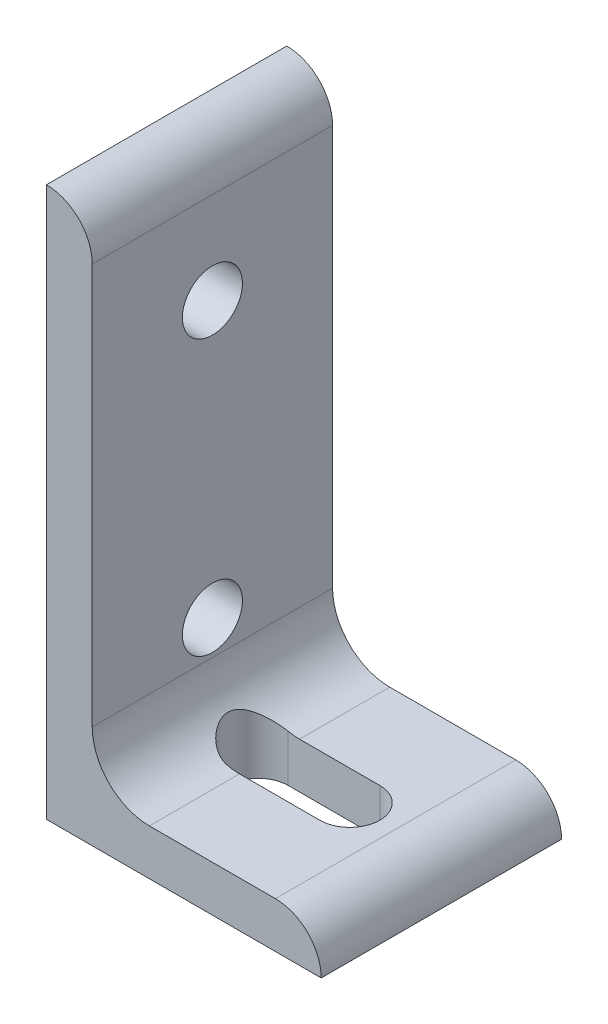
SolidWorks part; units mm, degrees
material "6105-T5 Aluminum"
ref_plane "Front Plane" through (0, 0, 0) normal (0, 0, 1) x (1, 0, 0)
ref_plane "Top Plane" through (0, 0, 0) normal (0, 1, 0) x (1, 0, 0)
ref_plane "Right Plane" through (0, 0, 0) normal (1, 0, 0) x (0, 0, -1)
sketch "Sketch2" plane through (0, 0, 0) normal (0, 0, 1) x (1, 0, 0)
  line L0 (0, 0) -> (0, 76.2)
  line L1 (38.1, 6.35) -> (38.1, 0)
  line L2 (6.35, 76.2) -> (6.35, 14.2748)
  line L3 (14.2748, 6.35) -> (38.1, 6.35)
  line L4 (0, 76.2) -> (6.35, 76.2)
  line L5 (38.1, 0) -> (0, 0)
  arc A2 (6.35, 14.2748) -> (14.2748, 6.35) centre (14.2748, 14.2748) ccw
  dimension "D3" = 76.2
  dimension "D4" = 7.9248
  dimension "D1" = 6.35
  dimension "D2" = 6.35
  dimension "D5" = 38.1
extrude "Boss-Extrude1" add sketch "Sketch2" along normal mid plane 33.3248
fillet "Fillet1" radius 6.35 2 edges at (38.1, 6.35, 0) (6.35, 76.2, 0)
sketch "Sketch3" plane through (0, 0, 0) normal (-1, 0, 0) x (0, 0, 1)
  line L1 (0, 57.15) -> (0, 19.05) construction
  line L2 (0, 0) -> (0, 19.05) construction
  circle A0 centre (0, 57.15) radius 4.1656
  circle A1 centre (0, 19.05) radius 4.1656
  dimension "D1" = 8.3312
  dimension "D2" = 38.1
  dimension "D3" = 19.05
extrude "Cut-Extrude1" cut sketch "Sketch3" against normal up to next
sketch "Sketch4" plane through (0, 0, 0) normal (0, -1, 0) x (1, 0, 0)
  line L1 (25.4, 4.1656) -> (12.7, 4.1656)
  line L2 (0, 0) -> (12.7, 0) construction
  line L3 (12.7, -4.1656) -> (25.4, -4.1656)
  line L4 (0, 16.6624) -> (0, -16.6624) construction
  arc A0 (25.4, -4.1656) -> (25.4, 4.1656) centre (25.4, 0) ccw
  arc A1 (12.7, 4.1656) -> (12.7, -4.1656) centre (12.7, 0) ccw
  dimension "D1" = 8.3312
  dimension "D2" = 12.7
  dimension "D3" = 12.7
extrude "Cut-Extrude2" cut sketch "Sketch4" against normal up to next
